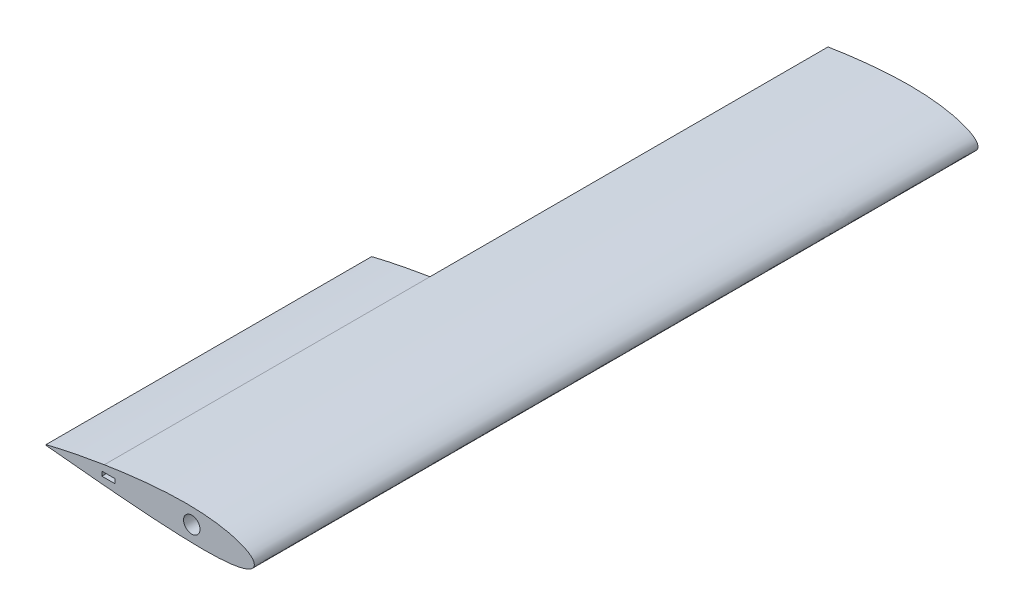
SolidWorks part; units mm, degrees
ref_plane "Front Plane" through (0, 0, 0) normal (0, 0, 1) x (1, 0, 0)
ref_plane "Top Plane" through (0, 0, 0) normal (0, 1, 0) x (1, 0, 0)
ref_plane "Right Plane" through (0, 0, 0) normal (1, 0, 0) x (0, 0, -1)
sketch "Sketch1" plane through (0, 0, 0) normal (0, 0, 1) x (1, 0, 0)
  line L0 (-232.0798, 18.6403) -> (-232.0798, -9.2995)
  spline S0 degree 3 poles (-232.0798, 18.6403) (-229.1643, 19.1051) (-222.2911, 20.2009) (-211.3375, 21.8003) (-199.1467, 23.4589) (-186.7095, 24.9978) (-174.1041, 26.3964) (-161.4086, 27.6282) (-148.7028, 28.67) (-136.0486, 29.4987) (-123.5023, 30.1004) (-111.1413, 30.381) (-99.0664, 30.3378) (-87.3818, 29.9639) (-76.166, 29.2625) (-65.4942, 28.2421) (-55.4376, 26.9176) (-46.0625, 25.3096) (-37.4298, 23.4441) (-29.5941, 21.3513) (-22.603, 19.0647) (-16.4967, 16.6189) (-11.3071, 14.0482) (-7.0567, 11.3833) (-3.7587, 8.6453) (-1.4211, 5.8377) (-0.0765, 2.934) (0.1754, -0.0176) (-0.6552, -2.8586) (-2.5307, -5.4396) (-5.3368, -7.7439) (-9.0399, -9.8146) (-13.6249, -11.6648) (-19.0703, -13.295) (-25.3465, -14.701) (-32.4168, -15.8791) (-40.2393, -16.8276) (-48.7681, -17.5483) (-57.9533, -18.0468) (-67.7426, -18.3331) (-78.0803, -18.4209) (-88.9087, -18.3281) (-100.1673, -18.0756) (-111.7935, -17.6875) (-123.7453, -17.1857) (-135.9735, -16.6041) (-148.4028, -15.8904) (-160.9356, -15.0745) (-173.4784, -14.1779) (-185.9552, -13.2219) (-198.2901, -12.2258) (-210.4075, -11.2062) (-221.6469, -10.2324) (-228.8379, -9.5894) (-232.0798, -9.2995) knots 0 0 0 0 0.018424 0.043434 0.06908 0.095203 0.12164 0.148227 0.1748 0.201195 0.227364 0.253182 0.278347 0.30271 0.326128 0.348467 0.3696 0.389416 0.407811 0.424699 0.440008 0.453688 0.465715 0.476104 0.484928 0.49236 0.49873 0.504587 0.510443 0.516804 0.524199 0.532941 0.543186 0.554996 0.568376 0.583299 0.599709 0.617539 0.636704 0.657109 0.678651 0.701217 0.724685 0.748928 0.773811 0.799338 0.825326 0.851504 0.877716 0.9038 0.929596 0.954944 0.979688 1 1 1 1
extrude "Boss-Extrude1" add sketch "Sketch1" against normal blind 1120
sketch "Sketch2" plane through (0, 0, 0) normal (0, 0, 1) x (1, 0, 0)
  line L0 (-232.0798, 18.6403) -> (-232.0798, -9.2995)
  line L1 (-322.333, 0.5148) -> (-322.333, -0.5066)
  spline S0 degree 3 poles (-232.0798, 18.6403) (-232.9971, 18.4966) (-237.5995, 17.7757) (-245.6979, 16.3987) (-256.1817, 14.5496) (-266.0705, 12.7084) (-275.3065, 10.9119) (-283.8343, 9.1839) (-291.6033, 7.5511) (-298.5679, 6.0388) (-304.6872, 4.6711) (-309.9259, 3.4706) (-314.2535, 2.4578) (-317.6452, 1.6505) (-320.0818, 1.0631) (-321.538, 0.709) (-322.1805, 0.552) (-322.333, 0.5148) knots 0 0 0 0 0.030252 0.151774 0.267626 0.37709 0.479485 0.574175 0.66057 0.73813 0.806369 0.864859 0.913229 0.951173 0.978451 0.994887 1 1 1 1
  spline S1 degree 3 poles (-232.0798, -9.2995) (-232.6657, -9.2475) (-236.9346, -8.868) (-244.7159, -8.1558) (-255.2335, -7.1827) (-265.179, -6.2448) (-274.4894, -5.353) (-283.1057, -4.5145) (-290.9725, -3.7372) (-298.0392, -3.0286) (-304.2602, -2.3953) (-309.5949, -1.8468) (-314.0082, -1.3828) (-317.4721, -1.0277) (-319.9612, -0.741) (-321.4641, -0.6201) (-322.142, -0.5059) (-322.3217, -0.5065) (-322.333, -0.5066) knots 0 0 0 0 0.019463 0.141781 0.258505 0.3689 0.472262 0.567931 0.655294 0.733785 0.802892 0.862162 0.911205 0.949694 0.977373 0.994054 0.999628 1 1 1 1
extrude "Boss-Extrude2" add sketch "Sketch2" against normal blind 504
sketch "Sketch3" plane through (0, 0, 0) normal (0, 0, 1) x (1, 0, 0)
  circle A0 centre (-96.7, 6.044) radius 12.7
extrude "Cut-Extrude1" cut sketch "Sketch3" against normal blind 801
ref_plane "Plane1" through (0, 0, -376.7) normal (0, 0, 1) x (1, 0, 0)
sketch "Sketch4" plane through (0, 0, -376.7) normal (0, 0, 1) x (1, 0, 0)
  line L0 (-112.7, -19.138) -> (-80.7, -19.138)
  line L1 (-80.7, -19.138) -> (-80.7, 21.744)
  line L2 (-80.7, 21.744) -> (-112.7, 21.744)
  line L3 (-112.7, 21.744) -> (-112.7, -19.138)
extrude "Cut-Extrude2" cut sketch "Sketch4" along normal blind 46
ref_plane "Plane2" through (0, 0, -376.7) normal (0, 0, 1) x (1, 0, 0)
sketch "Sketch5" plane through (0, 0, -376.7) normal (0, 0, 1) x (1, 0, 0)
  line L0 (-287.8664, -8.987) -> (-227.8664, -8.987)
  line L1 (-227.8664, -8.987) -> (-227.8664, 3.013)
  line L2 (-227.8664, 3.013) -> (-287.8664, 3.013)
  line L3 (-287.8664, 3.013) -> (-287.8664, -8.987)
extrude "Cut-Extrude3" cut sketch "Sketch5" along normal blind 46
ref_plane "Plane3" through (0, 0, -598.5) normal (0, 0, 1) x (1, 0, 0)
sketch "Sketch6" plane through (0, 0, -598.5) normal (0, 0, 1) x (1, 0, 0)
  line L0 (-204.283, -16.91) -> (-150.283, -16.91)
  line L1 (-150.283, -16.91) -> (-150.283, 12.19)
  line L2 (-150.283, 12.19) -> (-204.283, 12.19)
  line L3 (-204.283, 12.19) -> (-204.283, -16.91)
extrude "Cut-Extrude4" cut sketch "Sketch6" along normal blind 64
ref_plane "Plane4" through (0, 0, -25.5) normal (0, 0, 1) x (1, 0, 0)
sketch "Sketch7" plane through (0, 0, -25.5) normal (0, 0, 1) x (1, 0, 0)
  line L0 (-235.833, 1.435) -> (-215.433, 1.435)
  line L1 (-215.433, 1.435) -> (-215.433, 8.235)
  line L2 (-215.433, 8.235) -> (-235.833, 8.235)
  line L3 (-235.833, 8.235) -> (-235.833, 1.435)
extrude "Cut-Extrude5" cut sketch "Sketch7" along normal blind 26
ref_plane "Plane5" through (0, 0, -930) normal (0, 0, 1) x (1, 0, 0)
sketch "Sketch8" plane through (0, 0, -930) normal (0, 0, 1) x (1, 0, 0)
  line L0 (-60, -19.343) -> (-40, -19.343)
  line L1 (-40, -19.343) -> (-40, -15.343)
  line L2 (-40, -15.343) -> (-60, -15.343)
  line L3 (-60, -15.343) -> (-60, -19.343)
extrude "Cut-Extrude6" cut sketch "Sketch8" along normal blind 20
